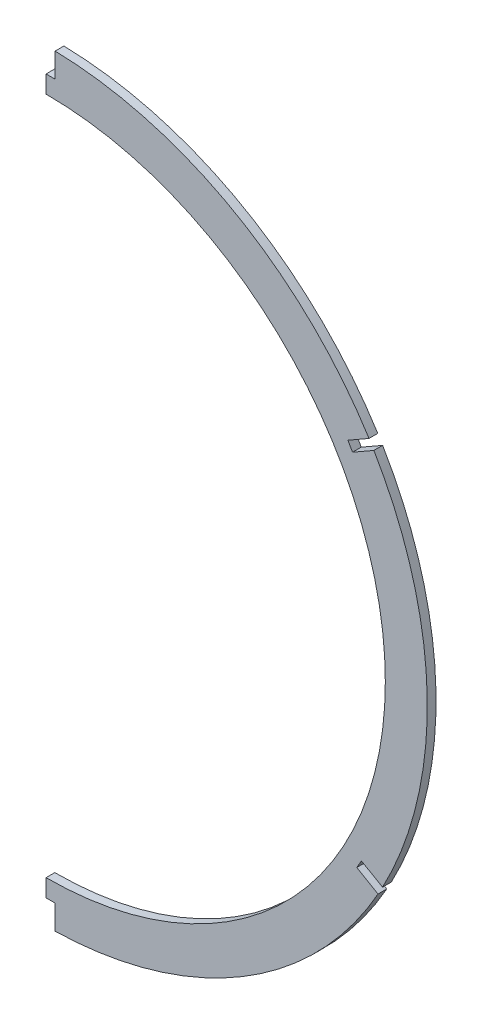
SolidWorks part; units mm, degrees
material "Balsa"
ref_plane "Front Plane" through (0, 0, 0) normal (0, 0, 1) x (1, 0, 0)
ref_plane "Top Plane" through (0, 0, 0) normal (0, 1, 0) x (1, 0, 0)
ref_plane "Right Plane" through (0, 0, 0) normal (1, 0, 0) x (0, 0, -1)
sketch "Sketch1" plane through (0, 0, 0) normal (0, 0, 1) x (1, 0, 0)
  line L0 (0, 32.094) -> (0, -346.2619) construction
  line L1 (0, 0) -> (0, 244.345) construction
  line L2 (0, 0) -> (0, 471.6969) construction
  line L3 (0, 0) -> (-283.5939, 0) construction
  line L4 (-127.2933, -32.5553) -> (-85.9841, -73.8644)
  line L5 (-85.9841, -73.8644) -> (-85.9841, -86.6438)
  line L6 (-85.9841, -73.8644) -> (-54.3993, -105.4493) construction
  arc A0 (-54.3993, -105.4493) -> (-127.2933, -32.5553) centre (0, 21.844) ccw
  arc A2 (-82.075, -89.6305) -> (-54.3993, -105.4493) centre (0, 21.844) ccw construction
  arc A3 (-127.2933, -32.5553) -> (-82.075, -89.6305) centre (0, 21.844) ccw construction
  arc A4 (-85.9841, -86.6438) -> (-54.3993, -105.4493) centre (0, 21.844) ccw
  spline S2 degree 3 poles (-19.218, -1838.2141) (276.9397, -392.4777) (232.9593, 72.7514) (49.9381, 150.9258) (45.7097, 152.4909) (37.1079, 155.2035) (32.7346, 156.3511) (27.1752, 157.5183) (26.0587, 157.7384) (23.8163, 158.1514) (22.6888, 158.3447) (19.306, 158.8811) (17.0511, 159.1813) (10.2867, 159.9126) (1.2693, 160.4377) (-7.745, 160.0789) (-14.5046, 159.4749) (-16.7575, 159.2176) (-20.1367, 158.7464) (-21.263, 158.5751) (-23.5156, 158.2037) (-24.6421, 158.0036) (-30.2426, 156.9366) (-34.6466, 155.8674) (-43.3063, 153.3113) (-47.562, 151.8242) (-55.9254, 148.4331) (-60.0331, 146.529) (-66.0807, 143.3516) (-68.0818, 142.2359) (-72.0044, 139.9197) (-73.9301, 138.7173) (-79.6017, 134.9792) (-86.884, 129.6473) (-93.6143, 123.6295) (-98.4521, 118.8554) (-100.0296, 117.2204) (-102.3424, 114.7015) (-103.1054, 113.8496) (-104.6077, 112.1297) (-105.3467, 111.2623) (-108.9818, 106.8875) (-111.6981, 103.2683) (-116.7574, 95.7975) (-119.1004, 91.9459) (-123.4121, 84.0098) (-125.3809, 79.9253) (-127.6006, 74.6695) (-128.0327, 73.61) (-128.8681, 71.4874) (-129.2719, 70.423) (-130.4422, 67.2205) (-131.1674, 65.0732) (-133.1812, 58.5951) (-135.4347, 49.861) (-136.834, 40.9354) (-137.5569, 34.168) (-137.7434, 31.9) (-137.9397, 28.4793) (-137.9911, 27.3374) (-138.0656, 25.0596) (-138.0887, 23.9223) (-138.135, 18.2442) (-137.9496, 13.7276) (-137.1441, 4.7454) (-136.5239, 0.2797) (-134.8456, -8.6005) (-133.7876, -13.015) (-131.2181, -21.791) (-129.7278, -26.0794) (-126.351, -34.4622) (-124.4643, -38.5569) (-120.2966, -46.5538) (-118.0156, -50.456) (-114.9122, -55.2108) (-114.2789, -56.1556) (-112.9868, -58.0327) (-112.3272, -58.9661) (-110.315, -61.7398) (-108.9333, -63.5482) (-104.6702, -68.8537) (-98.6716, -75.6089) (-92.0553, -81.7381) (-86.8592, -86.0978) (-85.0881, -87.5114) (-82.3719, -89.5716) (-81.4566, -90.2482) (-79.6058, -91.5811) (-78.6696, -92.238) (117.1329, -226.0075) (630.1685, 154.3992) (1500.4507, 1111.3958) knots -1.313799 -1.313799 -1.313799 -1.313799 0.03125 0.03125 0.0625 0.0625 0.09375 0.09375 0.101563 0.101563 0.109375 0.109375 0.125 0.125 0.15625 0.1875 0.1875 0.203125 0.203125 0.210937 0.210937 0.21875 0.21875 0.25 0.25 0.28125 0.28125 0.3125 0.3125 0.328125 0.328125 0.34375 0.34375 0.375 0.40625 0.40625 0.421875 0.421875 0.429687 0.429687 0.4375 0.4375 0.46875 0.46875 0.5 0.5 0.53125 0.53125 0.539062 0.539062 0.546875 0.546875 0.5625 0.5625 0.59375 0.625 0.625 0.640625 0.640625 0.648437 0.648437 0.65625 0.65625 0.6875 0.6875 0.71875 0.71875 0.75 0.75 0.78125 0.78125 0.8125 0.8125 0.84375 0.84375 0.851562 0.851562 0.859375 0.859375 0.875 0.875 0.90625 0.9375 0.9375 0.953125 0.953125 0.960937 0.960937 0.96875 0.96875 2.582348 2.582348 2.582348 2.582348 only from (66.3397, 143.1887) to (-66.0465, -100.0388)
  spline S3 degree 3 poles (66.3397, 143.1887) (62.3323, 145.3909) (58.2494, 147.3758) (49.9381, 150.9258) (45.7097, 152.4909) (37.1079, 155.2035) (32.7346, 156.3511) (27.1752, 157.5183) (26.0587, 157.7384) (23.8163, 158.1514) (22.6888, 158.3447) (19.306, 158.8811) (17.0511, 159.1813) (10.2867, 159.9126) (1.2693, 160.4377) (-7.745, 160.0789) (-14.5046, 159.4749) (-16.7575, 159.2176) (-20.1367, 158.7464) (-21.263, 158.5751) (-23.5156, 158.2037) (-24.6421, 158.0036) (-30.2426, 156.9366) (-34.6466, 155.8674) (-43.3063, 153.3113) (-47.562, 151.8242) (-55.9254, 148.4331) (-60.0331, 146.529) (-66.0807, 143.3516) (-68.0818, 142.2359) (-72.0044, 139.9197) (-73.9301, 138.7173) (-79.6017, 134.9792) (-86.884, 129.6473) (-93.6143, 123.6295) (-98.4521, 118.8554) (-100.0296, 117.2204) (-102.3424, 114.7015) (-103.1054, 113.8496) (-104.6077, 112.1297) (-105.3467, 111.2623) (-108.9818, 106.8875) (-111.6981, 103.2683) (-116.7574, 95.7975) (-119.1004, 91.9459) (-123.4121, 84.0098) (-125.3809, 79.9253) (-127.6006, 74.6695) (-128.0327, 73.61) (-128.8681, 71.4874) (-129.2719, 70.423) (-130.4422, 67.2205) (-131.1674, 65.0732) (-133.1812, 58.5951) (-135.4347, 49.861) (-136.834, 40.9354) (-137.5569, 34.168) (-137.7434, 31.9) (-137.9397, 28.4793) (-137.9911, 27.3374) (-138.0656, 25.0596) (-138.0887, 23.9223) (-138.135, 18.2442) (-137.9496, 13.7276) (-137.1441, 4.7454) (-136.5239, 0.2797) (-134.8456, -8.6005) (-133.7876, -13.015) (-131.2181, -21.791) (-129.7278, -26.0794) (-127.6847, -31.1513) (-127.3213, -32.0275) (-126.9491, -32.8995) knots 0 0 0 0 0.03125 0.03125 0.0625 0.0625 0.09375 0.09375 0.101563 0.101563 0.109375 0.109375 0.125 0.125 0.15625 0.1875 0.1875 0.203125 0.203125 0.210937 0.210937 0.21875 0.21875 0.25 0.25 0.28125 0.28125 0.3125 0.3125 0.328125 0.328125 0.34375 0.34375 0.375 0.40625 0.40625 0.421875 0.421875 0.429687 0.429687 0.4375 0.4375 0.46875 0.46875 0.5 0.5 0.53125 0.53125 0.539062 0.539062 0.546875 0.546875 0.5625 0.5625 0.59375 0.625 0.625 0.640625 0.640625 0.648437 0.648437 0.65625 0.65625 0.6875 0.6875 0.71875 0.71875 0.75 0.75 0.78125 0.78125 0.787815 0.787815 0.787815 0.787815 construction
  point P2 (0, 160.2226)
  point P3 (0, -116.9127)
  point P23 (-85.9841, -73.8644)
  dimension "D1" = 277.1353
  dimension "D2" = 276.86
  dimension "D3" = 21.844
  dimension "D5" = 45
  dimension "D6" = 113.03
  dimension "D4" = 58.42
  dimension "D7" = 45
extrude "Boss-Extrude1" add sketch "Sketch1" along normal mid plane 3.175
sketch "Sketch2" plane through (0, 0, 1.5875) normal (0, 0, 1) x (1, 0, 0)
  line L4 (-114.3729, -23.9231) -> (-70.7441, -67.5518)
  line L5 (-70.7441, -67.5518) -> (-70.7441, -79.0076)
  line L6 (-114.3729, -23.9231) -> (-70.7441, -67.5518)
  line L7 (-70.7441, -67.5518) -> (-70.7441, -79.0076)
  arc A2 (-70.7441, -79.0076) -> (-114.3729, -23.9231) centre (0, 21.844) ccw
  arc A3 (-70.7441, -79.0076) -> (-114.3729, -23.9231) centre (0, 21.844) ccw
  dimension "D1" = 15.24
extrude "Cut-Extrude1" cut sketch "Sketch2" against normal up to surface (3.175 mm away) up to face at (-27.5361, -9.1994, -1.5875)
fillet "Fillet1" radius 8.89 6 edges at (-127.2933, -32.5553, 0) (-114.3729, -23.9231, 0) (-85.9841, -73.8644, 0) (-85.9841, -86.6438, 0) (-70.7441, -67.5518, 0) (-70.7441, -79.0076, 0)
sketch "Sketch3" plane through (0, 0, 1.5875) normal (0, 0, 1) x (1, 0, 0)
  line L0 (0, 49.992) -> (0, 733.2) construction
  line L1 (0, 49.992) -> (0, 733.2) construction
  line L2 (-136.2041, -28.3557) -> (0, 49.992) construction
  line L3 (136.2041, -28.3557) -> (0, 49.992) construction
  line L4 (-136.2041, -28.3557) -> (0, 49.992) construction
  line L5 (136.2041, -28.3557) -> (0, 49.992) construction
  line L6 (-1.651, 152.6442) -> (-1.651, 160.2642)
  line L7 (1.651, 152.6442) -> (1.651, 160.2642)
  line L8 (-1.651, 152.6442) -> (1.651, 152.6442)
  line L9 (119.8454, -45.9681) -> (106.751, -38.3801)
  line L10 (121.4405, -43.2127) -> (108.3453, -35.6242)
  line L11 (-126.0584, -33.7901) -> (-88.588, -71.2606)
  line L12 (-85.9841, -77.5468) -> (-85.9841, -82.2574)
  line L13 (-126.0584, -33.7901) -> (-88.588, -71.2606) construction
  line L14 (-85.9841, -77.5468) -> (-85.9841, -82.2574) construction
  line L18 (121.4405, -43.2127) -> (108.3453, -35.6242)
  line L30 (-123.167, -47.8929) -> (-104.8699, -37.29)
  line L35 (119.8454, -45.9681) -> (106.751, -38.3801)
  line L36 (-109.2131, -37.6397) -> (-109.8693, -36.5073)
  line L47 (108.5244, -35.721) -> (120.1169, -46.1175) construction
  line L48 (114.3206, -40.9193) -> (126.5619, -48.0121) construction
  line L49 (113.8577, -42.5592) -> (122.0137, -47.2849)
  line L50 (115.5132, -39.7021) -> (123.6691, -44.4278)
  line L51 (113.8577, -42.5592) -> (115.5132, -39.7021)
  line L52 (122.0137, -47.2849) -> (123.6691, -44.4278)
  line L58 (-124.7703, -45.1423) -> (-109.8693, -36.5073)
  line L59 (-124.7703, -45.1423) -> (-123.167, -47.8929)
  line L67 (-105.8098, -35.6675) -> (-109.2131, -37.6397)
  line L71 (-124.7703, -45.1423) -> (-123.167, -47.8929) construction
  line L72 (-124.7703, -45.1423) -> (-109.8693, -36.5073) construction
  line L73 (-123.167, -47.8929) -> (-104.8699, -37.29) construction
  line L74 (-123.167, -47.8929) -> (-107.9499, -35.3951) construction
  line L75 (-115.5584, -41.644) -> (-110.9064, -38.9482) construction
  line L76 (-119.3826, -41.9518) -> (-112.6266, -38.0369)
  line L77 (-117.727, -44.8088) -> (-110.971, -40.8938)
  line L78 (-119.3826, -41.9518) -> (-117.727, -44.8088)
  line L79 (-112.6266, -38.0369) -> (-110.971, -40.8938)
  line L82 (-105.8098, -35.6675) -> (-109.2131, -37.6397) construction
  line L83 (-109.2131, -37.6397) -> (-109.8693, -36.5073) construction
  arc A0 (-54.3993, -105.4493) -> (-127.2933, -32.5553) centre (0, 21.844) ccw construction
  arc A2 (-1.651, 160.2642) -> (-130.2816, -24.9489) centre (0, 21.844) ccw construction
  arc A3 (-130.2816, -24.9489) -> (-127.2933, -32.5553) centre (0, 21.844) ccw construction
  arc A4 (-1.651, 160.2642) -> (-130.2816, -24.9489) centre (0, 21.844) ccw construction
  arc A5 (-130.2816, -24.9489) -> (-127.9919, -30.8906) centre (0, 21.844) ccw construction
  arc A6 (-82.3849, -89.4016) -> (-127.9919, -30.8906) centre (0, 21.844) ccw
  arc A7 (-127.9919, -30.8906) -> (-126.0584, -33.7901) centre (-119.7722, -27.504) ccw
  arc A8 (-85.9841, -77.5468) -> (-88.588, -71.2606) centre (-94.8741, -77.5468) ccw
  arc A9 (-85.9841, -82.2574) -> (-82.3849, -89.4016) centre (-77.0941, -82.2574) ccw
  arc A11 (-127.9919, -30.8906) -> (-126.0584, -33.7901) centre (-119.7722, -27.504) ccw construction
  arc A12 (-85.9841, -77.5468) -> (-88.588, -71.2606) centre (-94.8741, -77.5468) ccw construction
  arc A13 (-85.9841, -82.2574) -> (-82.3849, -89.4016) centre (-77.0941, -82.2574) ccw construction
  arc A14 (130.2816, -24.9489) -> (1.651, 160.2642) centre (0, 21.844) ccw construction
  arc A15 (1.651, 160.2642) -> (-1.651, 160.2642) centre (0, 21.844) ccw
  arc A16 (130.2816, -24.9489) -> (1.651, 160.2642) centre (0, 21.844) ccw construction
  arc A17 (1.651, 160.2642) -> (-1.651, 160.2642) centre (0, 21.844) ccw
  spline S0 degree 3 poles (106.751, -38.3801) (107.2824, -37.4615) (107.8139, -36.5429) (108.3453, -35.6242) knots 0 0 0 0 1 1 1 1 weights 1 1 1 1
  spline S1 degree 3 poles (119.8454, -45.9681) (120.3771, -45.0496) (120.9088, -44.1312) (121.4405, -43.2127) knots 0 0 0 0 1 1 1 1 weights 1 1 1 1
  spline S2 degree 3 poles (-885.9995, -1769.7517) (-211.5636, -622.9991) (457.4593, 532.6423) (1115.3786, 1687.3419) knots -628.025775 -628.025775 -628.025775 -628.025775 629.321979 629.321979 629.321979 629.321979 weights 1.00213 0.999289 0.99929 1.002132 only from (119.8454, -45.9681) to (121.4405, -43.2127)
  spline S3 degree 3 poles (-1102.3122, 1695.2927) (-441.4553, 540.1286) (227.4994, -614.6331) (901.0143, -1762.8764) knots -1066.678373 -1066.678373 -1066.678373 -1066.678373 1067.563855 1067.563855 1067.563855 1067.563855 weights 1.001327 0.999558 0.999558 1.001327 only from (-105.8098, -35.6675) to (-104.8699, -37.29)
  spline S4 degree 3 poles (-105.8098, -35.6675) (-105.4965, -36.2084) (-105.1832, -36.7492) (-104.8699, -37.29) knots 0 0 0 0 1 1 1 1 weights 1 1 1 1 construction
  spline S6 degree 3 poles (-898.4881, -1762.9922) (-224.3422, -615.0331) (444.2887, 540.7283) (1102.2727, 1695.4213) knots -627.922306 -627.922306 -627.922306 -627.922306 629.42597 629.42597 629.42597 629.42597 weights 1.001921 0.999359 0.99936 1.001924 only from (106.751, -38.3801) to (108.3453, -35.6242)
  point P49 (-116.0256, -43.8229)
  point P50 (120.451, -46.3794)
  arc M19 (-82.3849, -89.4016) -> (-127.9919, -30.8906) centre (0, 21.844) ccw
  line M21 (-126.0584, -33.7901) -> (-88.588, -71.2606)
  dimension "D1" = 3.302
  dimension "D2" = 7.62
  dimension "D4" = 3.302
  dimension "D5" = 7.62
  dimension "D6" = 3.302
  dimension "D7" = 5.842
  dimension "D3" = 0
extrude "Cut-Extrude2" [suppressed] cut sketch "Sketch3" against normal through all contours L79 L76 L77 M21 | L6 L8 L7 M19 | L51 L49 L50 M19
sketch "Sketch4" plane through (0, 0, 0) normal (1, 0, 0) x (0, 0, -1)
  line L1 (-96.2805, 232.7957) -> (122.2438, 232.7957)
  line L2 (-96.2805, 232.7957) -> (-96.2805, -207.8589)
  line L3 (-96.2805, -207.8589) -> (122.2438, -207.8589)
  line L4 (122.2438, 232.7957) -> (122.2438, -207.8589)
extrude "Cut-Extrude3" cut sketch "Sketch4" against normal through all
sketch "Sketch5" plane through (0, 0, -1.5875) normal (0, 0, -1) x (-1, 0, 0)
  line L0 (0, 0) -> (0, 145.034) construction
  line L1 (0, 145.034) -> (0, 151.384) construction
  line L2 (104.929, 86.3862) -> (0, 26.2525) construction
  line L3 (-3.302, 151.384) -> (3.302, 151.384)
  line L4 (0, 151.384) -> (0, 164.084)
  line L5 (-3.302, 164.084) -> (3.302, 164.084)
  line L6 (3.302, 151.384) -> (3.302, 164.084)
  line L7 (104.929, 86.3862) -> (110.4384, 89.5435) construction
  line L8 (109.5985, 91.009) -> (111.2782, 88.078)
  line L9 (109.5985, 91.009) -> (120.6173, 97.3238)
  line L10 (111.2782, 88.078) -> (122.297, 94.3928)
  line L11 (120.6173, 97.3238) -> (122.297, 94.3928)
  line L12 (108.1767, -37.0931) -> (0, 25.5937) construction
  line L13 (108.1767, -37.0931) -> (113.6709, -40.2769) construction
  line L14 (112.824, -41.7383) -> (114.5178, -38.8154)
  line L15 (112.824, -41.7383) -> (123.8123, -48.1059)
  line L16 (114.5178, -38.8154) -> (125.5061, -45.183)
  line L17 (123.8123, -48.1059) -> (125.5061, -45.183)
  line L18 (0, 0) -> (0, -101.346) construction
  line L19 (0, -101.346) -> (0, -107.696) construction
  line L20 (-3.302, -107.696) -> (3.302, -107.696)
  line L21 (0, -107.696) -> (0, -120.396)
  line L22 (-3.302, -120.396) -> (3.302, -120.396)
  line L23 (3.302, -107.696) -> (3.302, -120.396)
  line L24 (-108.1767, -37.0931) -> (-113.6709, -40.2769) construction
  line L25 (-108.1767, -37.0931) -> (0, 25.5937) construction
  line L26 (-104.929, 86.3862) -> (-110.4384, 89.5435) construction
  line L27 (-104.929, 86.3862) -> (0, 26.2525) construction
  line L28 (-3.302, -107.696) -> (-3.302, -120.396)
  line L29 (-123.8123, -48.1059) -> (-125.5061, -45.183)
  line L30 (-114.5178, -38.8154) -> (-125.5061, -45.183)
  line L31 (-112.824, -41.7383) -> (-123.8123, -48.1059)
  line L32 (-112.824, -41.7383) -> (-114.5178, -38.8154)
  line L33 (-120.6173, 97.3238) -> (-122.297, 94.3928)
  line L34 (-111.2782, 88.078) -> (-122.297, 94.3928)
  line L35 (-109.5985, 91.009) -> (-120.6173, 97.3238)
  line L36 (-109.5985, 91.009) -> (-111.2782, 88.078)
  line L37 (-3.302, 151.384) -> (-3.302, 164.084)
  point P2 (110.4384, 89.5435)
  point P12 (113.6709, -40.2769)
  arc M20 (0, 160.274) -> (0, -116.586) centre (0, 21.844) ccw
  line M21 (0, -116.586) -> (0, -101.346)
  line M23 (0, 145.034) -> (0, 160.274)
  dimension "D1" = 59.908
  dimension "D2" = 60.183
  dimension "D3" = 145.034
  dimension "D4" = 3.302
  dimension "D5" = 12.7
  dimension "D6" = 6.35
  dimension "D7" = 120.9386
  dimension "D8" = 6.35
  dimension "D9" = 125.0273
  dimension "D10" = 6.35
  dimension "D11" = 3.3782
  dimension "D12" = 12.7
  dimension "D13" = 26.2525
  dimension "D14" = 25.5937
  dimension "D15" = 6.35
  dimension "D16" = 101.346
  dimension "D17" = 3.302
  dimension "D18" = 12.7
  dimension "D19" = 12.7
  dimension "D20" = 3.3782
extrude "Cut-Extrude4" cut sketch "Sketch5" against normal through all contours L31 L32 L30 M20 | L36 L35 L34 M20 | L37 L3 M23 M20 | L20 L28 M20 M21 region at (1.6498, 155.8224, -1.5875) region at (1.6498, -112.1344, -1.5875) region at (117.5161, -42.508, -1.5875) region at (114.2978, 91.7519, -1.5875)
equation "\"a\"= 0.06"
equation "\"slotwidth\"=0.13"
equation "\"slotheight\"=0.3"
